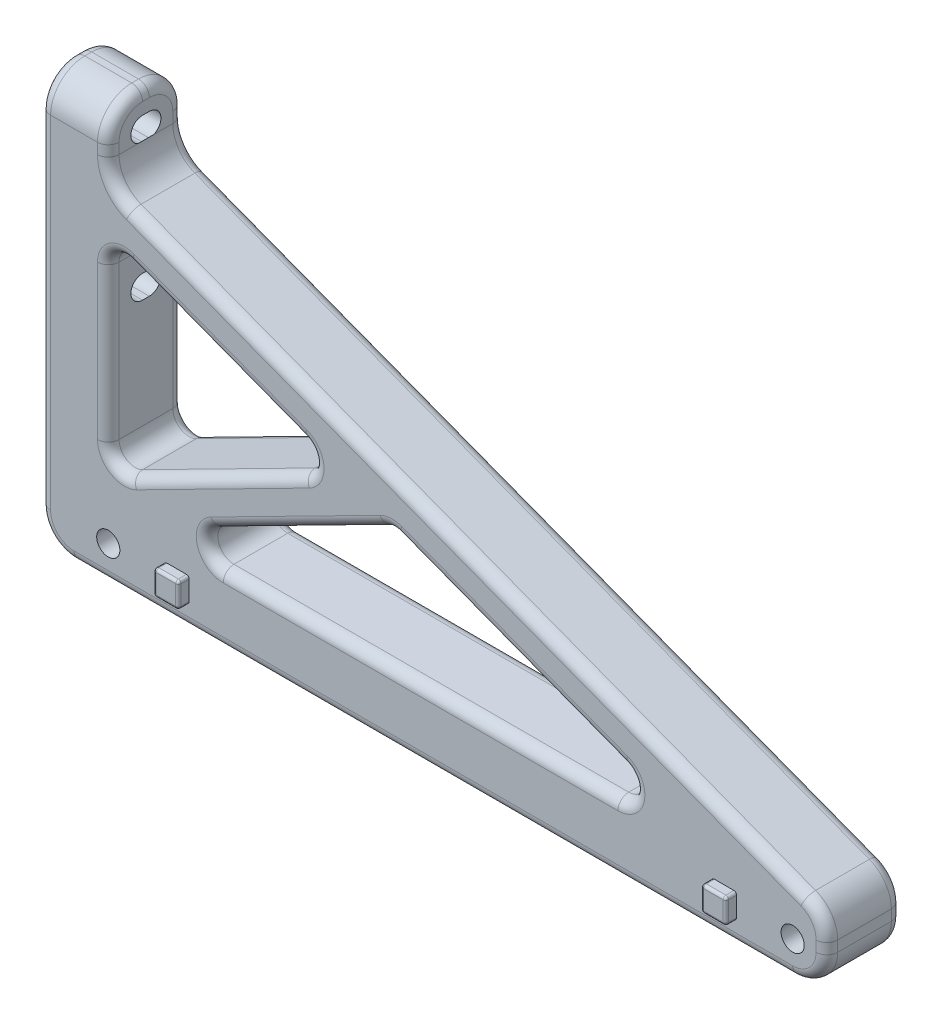
SolidWorks part; units mm, degrees
ref_plane "Front Plane" through (0, 0, 0) normal (0, 0, 1) x (1, 0, 0)
ref_plane "Top Plane" through (0, 0, 0) normal (0, 1, 0) x (1, 0, 0)
ref_plane "Right Plane" through (0, 0, 0) normal (1, 0, 0) x (0, 0, -1)
sketch "Sketch1" plane through (0, 0, 0) normal (0, 0, 1) x (1, 0, 0)
  line L0 (-12.7, 57.15) -> (-12.7, -6.35)
  line L1 (-12.7, -6.35) -> (133.35, -6.35)
  line L2 (133.35, -6.35) -> (133.35, 6.35)
  line L3 (133.35, 6.35) -> (0, 57.15)
  line L4 (0, 57.15) -> (-12.7, 57.15)
  line L5 (0, 48.5892) -> (0, 6.35)
  line L6 (0, 6.35) -> (110.8778, 6.35)
  line L7 (110.8778, 6.35) -> (0, 48.5892)
  line L8 (0, 6.35) -> (47.472, 30.5046) construction
  line L9 (8.8205, 6.35) -> (52.516, 28.5831)
  line L10 (0, 10.838) -> (42.428, 32.4261)
  line L12 (-12.7, 57.15) -> (0, 57.15)
  line L13 (-12.7, 57.15) -> (-12.7, 69.85)
  line L14 (-12.7, 69.85) -> (0, 69.85)
  line L15 (0, 57.15) -> (0, 69.85)
  circle A0 centre (0, 0) radius 2.15
  circle A1 centre (127, 0) radius 2.15
  point P21 (0, 0)
  dimension "D1" = 4.3
  dimension "D2" = 127
  dimension "D3" = 6.35
  dimension "D4" = 12.7
  dimension "D5" = 6.35
  dimension "D6" = 12.7
  dimension "D7" = 63.5
  dimension "D8" = 12.7
  dimension "D9" = 12.7
  dimension "D10" = 8
  dimension "D11" = 8
  dimension "D12" = 12.7
  dimension "D13" = 50.8
extrude "Boss-Extrude1" add sketch "Sketch1" along normal blind 13.97 contours L3 | L3 L4 L0 L1 L2 A1 A0 L7 L6 L5 | L5 L8 L7 L10 | L8 L6 L9 L7 | L4 L15 L14 L13 region at (-6.35, 55.5574, 0) region at (-6.35, 63.5, 0) region at (22.4986, 19.9997, 0) region at (27.1543, 17.9535, 0)
fillet "Fillet1" radius 3 6 edges at (110.8778, 6.35, 6.985) (52.516, 28.5831, 6.985) (8.8205, 6.35, 6.985) (0, 10.838, 6.985) (42.428, 32.4261, 6.985) (0, 48.5892, 6.985)
fillet "Fillet2" radius 6.35 6 edges at (133.35, 6.35, 6.985) (133.35, -6.35, 6.985) (-12.7, -6.35, 6.985) (0, 57.15, 6.985) (-6.35, 69.85, 0) (-6.35, 69.85, 13.97)
sketch "Sketch2" plane through (0, 0, 0) normal (1, 0, 0) x (0, 0, -1)
  line L1 (-7.62, 63.5) -> (-6.35, 63.5) construction
  line L2 (-7.62, 65.65) -> (-6.35, 65.65)
  line L3 (-7.62, 61.35) -> (-6.35, 61.35)
  line L4 (0, 61.5261) -> (0, 63.5) construction
  line L5 (-13.97, 61.5261) -> (-13.97, 55.5921) construction
  line L6 (-7.62, 69.85) -> (-6.35, 69.85) construction
  line L7 (-7.62, 35.95) -> (-6.35, 35.95)
  line L8 (-7.62, 40.25) -> (-6.35, 40.25)
  line L9 (-7.62, 38.1) -> (-6.35, 38.1) construction
  arc A1 (-7.62, 65.65) -> (-7.62, 61.35) centre (-7.62, 63.5) ccw
  arc A2 (-6.35, 61.35) -> (-6.35, 65.65) centre (-6.35, 63.5) ccw
  arc A3 (-7.62, 40.25) -> (-7.62, 35.95) centre (-7.62, 38.1) ccw
  arc A4 (-6.35, 35.95) -> (-6.35, 40.25) centre (-6.35, 38.1) ccw
  point P2 (-6.985, 63.5)
  point P16 (-6.985, 38.1)
  dimension "D1" = 2.15
  dimension "D2" = 6.35
  dimension "D3" = 6.35
  dimension "D4" = 6.35
  dimension "D6" = 25.4
  dimension "D5" = 2
extrude "Cut-Extrude1" cut sketch "Sketch2" against normal through all
fillet "Fillet3" radius 2 48 edges at (1.4318, 13.173, 0) (0, 29.9832, 0) (1.2976, 46.7062, 0) (20.0864, 40.9372, 0) (38.0326, 32.1914, 0) (97.5262, 8.807, 0) (57.9538, 6.35, 0) (18.4146, 8.6505, 0) (35.651, 20.0018, 0) (52.531, 28.3018, 0) (18.4146, 8.6505, 13.97) (57.9538, 6.35, 13.97) (97.5262, 8.807, 13.97) (74.7013, 20.1315, 13.97) (52.531, 28.3018, 13.97) (38.0326, 32.1914, 13.97) (20.3789, 21.2072, 13.97) (1.4318, 13.173, 13.97) (0, 29.9832, 13.97) (1.2976, 46.7062, 13.97) (132.2286, 5.5772, 13.97) (133.35, 0.9869, 13.97) (131.4901, -4.4901, 13.97) (60.325, -6.35, 13.97) (-10.8401, -4.4901, 13.97) (-12.7, 31.75, 13.97) (-12.7, 67.9901, 12.1101) (-12.7, 69.85, 6.985) (-12.7, 67.9901, 1.8599) (-12.7, 31.75, 0) (-10.8401, -4.4901, 0) (60.325, -6.35, 0) (131.4901, -4.4901, 0) (133.35, 0.9869, 0) (132.2286, 5.5772, 0) (66.675, 31.75, 0) (1.1214, 57.9228, 0) (0, 62.5131, 0) (0, 67.9901, 1.8599) (0, 69.85, 6.985) (0, 67.9901, 12.1101) (0, 62.5131, 13.97) (1.1214, 57.9228, 13.97) (20.3789, 21.2072, 0) (74.7013, 20.1315, 0) (35.651, 20.0018, 13.97) (20.0864, 40.9372, 13.97) (66.675, 31.75, 13.97)
sketch "Sketch3" plane through (0, 0, 13.97) normal (0, 0, 1) x (1, 0, 0)
  line L1 (0, 0) -> (127, 0) construction
  line L3 (10.3886, 2.3114) -> (15.0114, 2.3114)
  line L4 (10.3886, 2.3114) -> (10.3886, -2.3114)
  line L5 (10.3886, -2.3114) -> (15.0114, -2.3114)
  line L6 (15.0114, 2.3114) -> (15.0114, -2.3114)
  line L7 (10.3886, 2.3114) -> (15.0114, -2.3114) construction
  line L8 (10.3886, -2.3114) -> (15.0114, 2.3114) construction
  line L9 (111.9886, 2.3114) -> (116.6114, 2.3114)
  line L10 (111.9886, 2.3114) -> (111.9886, -2.3114)
  line L11 (111.9886, -2.3114) -> (116.6114, -2.3114)
  line L12 (116.6114, 2.3114) -> (116.6114, -2.3114)
  line L13 (111.9886, 2.3114) -> (116.6114, -2.3114) construction
  line L14 (111.9886, -2.3114) -> (116.6114, 2.3114) construction
  point P0 (12.7, 0)
  point P9 (114.3, 0)
  point P14 (116.6114, 0)
  dimension "D1" = 4.6228
  dimension "D2" = 12.7
  dimension "D3" = 4.6228
  dimension "D4" = 12.7
extrude "Boss-Extrude2" add sketch "Sketch3" along normal blind 2
fillet "Fillet4" radius 0.508 16 edges at (114.3, -2.3114, 15.97) (111.9886, 0, 15.97) (114.3, 2.3114, 15.97) (116.6114, 0, 15.97) (12.7, -2.3114, 15.97) (10.3886, 0, 15.97) (12.7, 2.3114, 15.97) (15.0114, 0, 15.97) (116.6114, 2.3114, 14.97) (116.6114, -2.3114, 14.97) (111.9886, -2.3114, 14.97) (111.9886, 2.3114, 14.97) (10.3886, -2.3114, 14.97) (15.0114, -2.3114, 14.97) (10.3886, 2.3114, 14.97) (15.0114, 2.3114, 14.97)
